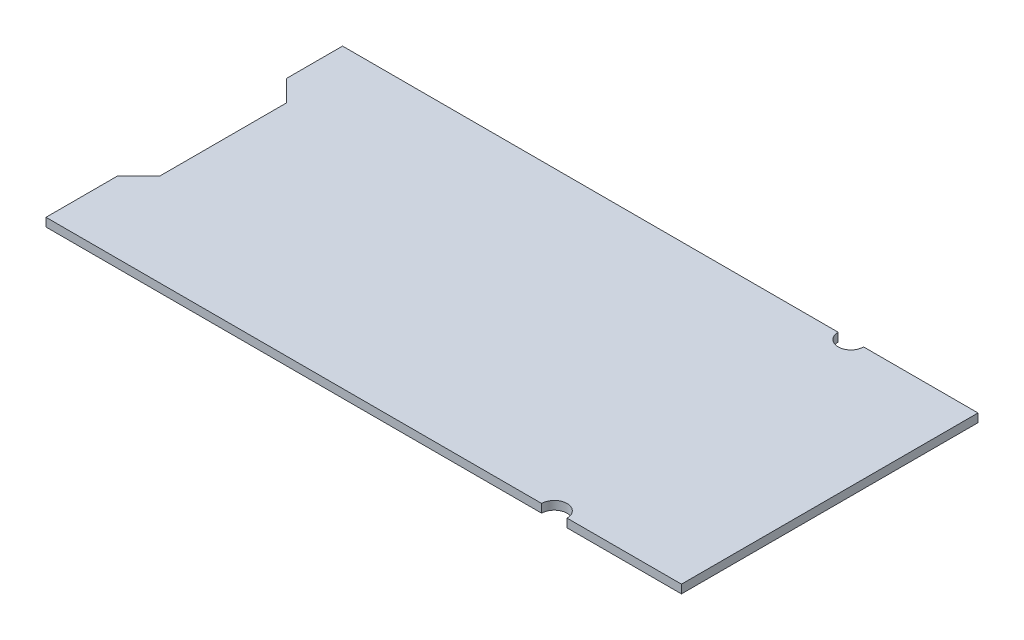
SolidWorks part; units mm, degrees
ref_plane "Front Plane" through (0, 0, 0) normal (0, 0, 1) x (1, 0, 0)
ref_plane "Top Plane" through (0, 0, 0) normal (0, 1, 0) x (1, 0, 0)
ref_plane "Right Plane" through (0, 0, 0) normal (1, 0, 0) x (0, 0, -1)
sketch "Sketch1" plane through (0, 0, 0) normal (0, 1, 0) x (1, 0, 0)
  line L1 (-37.5, 17.5) -> (37.5, 17.5)
  line L2 (-37.5, 17.5) -> (-37.5, -17.5)
  line L3 (-37.5, -17.5) -> (37.5, -17.5)
  line L4 (37.5, 17.5) -> (37.5, -17.5)
  line L5 (-37.5, 17.5) -> (37.5, -17.5) construction
  line L6 (-37.5, -17.5) -> (37.5, 17.5) construction
  point P0 (0, 0)
  dimension "D1" = 35
  dimension "D2" = 75
extrude "Boss-Extrude1" add sketch "Sketch1" along normal blind 1
sketch "Sketch2" plane through (0, 1, 0) normal (0, 1, 0) x (1, 0, 0)
  line L0 (-37.5, 17.5) -> (-37.5, -17.5) construction
  line L1 (-40, 10.89) -> (-35, 10.89)
  line L2 (-40, 10.89) -> (-40, -9.11)
  line L3 (-40, -9.11) -> (-35, -9.11)
  line L4 (-35, 10.89) -> (-35, -9.11)
  line L5 (-42.6707, 0.89) -> (-37.3293, 0.89) construction
  line L6 (37.5, 17.5) -> (-37.5, 17.5) construction
  line L7 (37.5, -17.5) -> (37.5, 17.5) construction
  circle A0 centre (22.5, 17.5) radius 1.5
  circle A1 centre (22.5, -17.5) radius 1.5
  point P0 (-37.5, 0)
  point P10 (-40, 0.89)
  point P11 (-37.5, 10.89)
  dimension "D3" = 15
  dimension "D1" = 5
  dimension "D2" = 20
  dimension "D5" = 16.61
extrude "Cut-Extrude1" cut sketch "Sketch2" against normal blind 10
chamfer "Chamfer1" distance 2.5 angle 45 2 edges at (-35, 0.5, 9.11) (-35, 0.5, -10.89)
